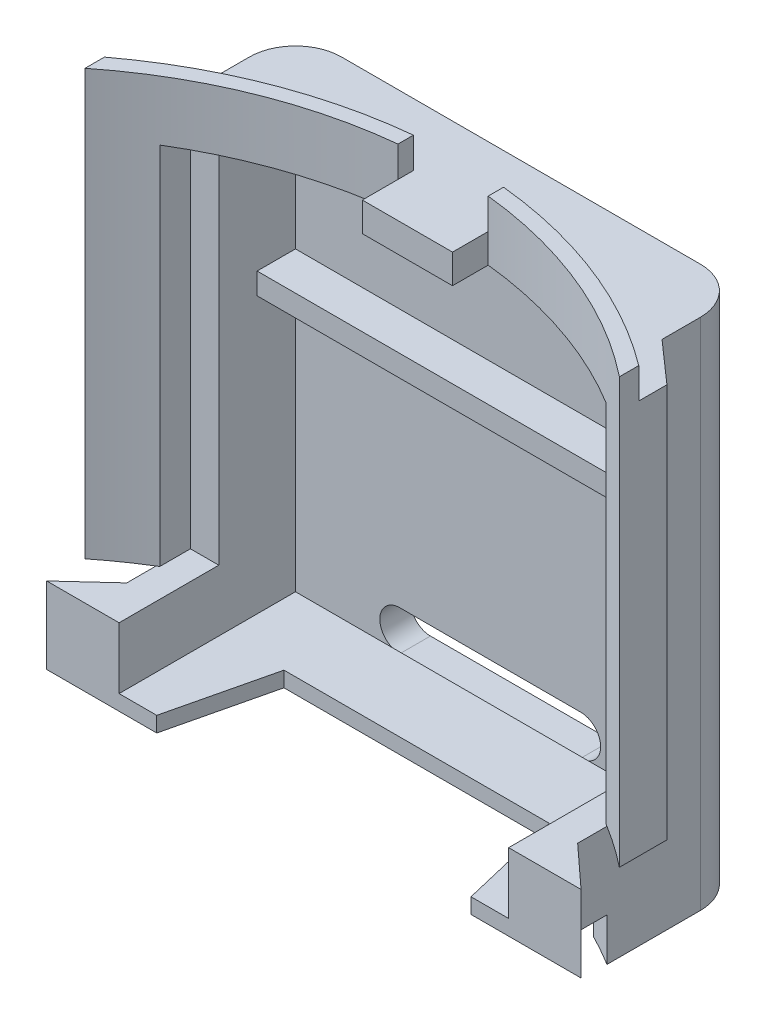
SolidWorks part; units mm, degrees
ref_plane "Спереди" through (0, 0, 0) normal (0, 0, 1) x (1, 0, 0)
ref_plane "Сверху" through (0, 0, 0) normal (0, 1, 0) x (1, 0, 0)
ref_plane "Справа" through (0, 0, 0) normal (1, 0, 0) x (0, 0, -1)
sketch "Эскиз1" plane through (0, 0, 0) normal (0, 1, 0) x (1, 0, 0)
  line L0 (-7.35, 2.75) -> (-7.35, 5.5)
  line L1 (-7.35, 5.5) -> (7.35, 5.5)
  line L2 (7.35, 5.5) -> (7.35, 2.75)
  line L3 (0, 0) -> (0, 5.5) construction
  line L4 (-8.71, 1.55) -> (-8.71, 0)
  line L5 (8.71, 1.55) -> (8.71, 0)
  line L6 (-8.71, 0) -> (8.71, 0) construction
  line L7 (-8.71, 1.55) -> (-7.35, 2.75)
  line L8 (8.71, 1.55) -> (7.35, 2.75)
  arc A0 (-8.71, 0) -> (8.71, 0) centre (0, -10.9607) cw
  dimension "D2" = 14
  dimension "D1" = 14.7
  dimension "D3" = 17.42
  dimension "D4" = 2.75
  dimension "D5" = 5.5
  dimension "D6" = 1.55
extrude "Бобышка-Вытянуть1" add sketch "Эскиз1" along normal blind 17.75
sketch "Эскиз2" plane through (0, 17.75, 0) normal (0, 1, 0) x (1, 0, 0)
  line L0 (8.71, 0) -> (8.71, 1.55) construction
  line L1 (8.71, 1.55) -> (7.35, 2.75) construction
  line L2 (7.35, 2.75) -> (7.35, 5.5) construction
  line L3 (7.35, 5.5) -> (-7.35, 5.5) construction
  line L4 (-7.35, 5.5) -> (-7.35, 2.75) construction
  line L5 (-7.35, 2.75) -> (-8.71, 1.55) construction
  line L6 (-8.71, 1.55) -> (-8.71, 0) construction
  line L7 (8.71, 0.6318) -> (8.71, 1.55)
  line L8 (8.71, 1.55) -> (7.35, 2.75)
  line L9 (7.35, 2.75) -> (7.35, 5.5)
  line L10 (7.35, 5.5) -> (-7.35, 5.5)
  line L11 (-7.35, 5.5) -> (-7.35, 2.75)
  line L12 (-7.35, 2.75) -> (-8.71, 1.55)
  line L13 (-8.71, 1.55) -> (-8.71, 0.6318)
  arc A0 (-8.71, 0.6318) -> (8.71, 0.6318) centre (0, -10.9607) cw
  arc A1 (8.71, 0) -> (-8.71, 0) centre (0, -10.9607) ccw construction
  dimension "D1" = 0.5
extrude "Вырез-Вытянуть1" cut sketch "Эскиз2" against normal blind 1
sketch "Эскиз3" plane through (0, 0, -5.5) normal (0, 0, -1) x (-1, 0, 0)
  line L0 (8.71, 16.75) -> (-8.71, 16.75) construction
  line L1 (-1.47, 17.75) -> (1.47, 17.75)
  line L2 (-1.47, 17.75) -> (-1.47, 16.75)
  line L3 (-1.47, 16.75) -> (1.47, 16.75)
  line L4 (1.47, 17.75) -> (1.47, 16.75)
  line L5 (-1.47, 17.75) -> (1.47, 16.75) construction
  line L6 (-1.47, 16.75) -> (1.47, 17.75) construction
  line L7 (8.71, 17.75) -> (-8.71, 17.75) construction
  point P0 (0, 17.25)
  dimension "D1" = 2.94
extrude "Вырез-Вытянуть2" cut sketch "Эскиз3" against normal through all
sketch "Эскиз4" plane through (0, 0, 0) normal (0, -1, 0) x (1, 0, 0)
  line L0 (-7.35, -2.75) -> (-7.35, -0.9548)
  line L1 (7.35, -2.75) -> (7.35, -0.9548)
  line L2 (-7.35, -2.75) -> (-8.71, -1.55) construction
  line L3 (-8.71, -1.55) -> (-8.71, 0) construction
  line L4 (8.71, -1.55) -> (7.35, -2.75) construction
  line L5 (8.71, 0) -> (8.71, -1.55) construction
  line L6 (-7.35, -2.75) -> (-8.71, -1.55)
  line L7 (-8.71, -1.55) -> (-8.71, 0)
  line L8 (8.71, -1.55) -> (7.35, -2.75)
  line L9 (8.71, 0) -> (8.71, -1.55)
  arc A0 (-8.71, 0) -> (8.71, 0) centre (0, 10.9607) ccw construction
  arc A1 (-8.71, 0) -> (-7.35, -0.9548) centre (0, 10.9607) ccw
  arc A2 (7.35, -0.9548) -> (8.71, 0) centre (0, 10.9607) ccw
extrude "Вырез-Вытянуть3" cut sketch "Эскиз4" against normal blind 3.9
sketch "Эскиз5" plane through (0, 0, 0) normal (0, -1, 0) x (1, 0, 0)
  line L0 (-7.35, -5.5) -> (-7.35, -0.9548) construction
  line L1 (-6.35, -1.5164) -> (6.35, -1.5164)
  line L2 (-6.35, -1.5164) -> (-6.35, -4.5)
  line L3 (-6.35, -4.5) -> (6.35, -4.5)
  line L4 (6.35, -1.5164) -> (6.35, -4.5)
  line L5 (-6.35, -1.5164) -> (6.35, -4.5) construction
  line L6 (-6.35, -4.5) -> (6.35, -1.5164) construction
  line L7 (7.35, -5.5) -> (-7.35, -5.5) construction
  arc A0 (-7.35, -0.9548) -> (7.35, -0.9548) centre (0, 10.9607) ccw construction
  point P0 (0, -3.0082)
  dimension "D1" = 1
  dimension "D2" = 1
extrude "Вырез-Вытянуть4" cut sketch "Эскиз5" against normal blind 1.4
ref_plane "Плоскость1" through (0, 1.9, 0) normal (0, -1, 0) x (-1, 0, 0)
sketch "Эскиз6" plane through (0, 1.9, 0) normal (0, -1, 0) x (-1, 0, 0)
  line L4 (-6.35, 1.5164) -> (6.35, 1.5164)
  line L5 (-6.35, 4.5) -> (-6.35, 1.5164)
  line L6 (6.35, 4.5) -> (-6.35, 4.5)
  line L7 (6.35, 1.5164) -> (6.35, 4.5)
  line L8 (-6.35, 1.5164) -> (6.35, 1.5164)
  line L9 (-6.35, 4.5) -> (-6.35, 1.5164)
  line L10 (6.35, 4.5) -> (-6.35, 4.5)
  line L11 (6.35, 1.5164) -> (6.35, 4.5)
  dimension "D1" = 0
extrude "Вырез-Вытянуть5" cut sketch "Эскиз6" against normal blind 13.9
ref_plane "Плоскость2" through (0, 0, -2) normal (0, 0, -1) x (-1, 0, 0)
sketch "Эскиз7" plane through (0, 0, -2) normal (0, 0, -1) x (-1, 0, 0)
  line L0 (6.35, 15.8) -> (-6.35, 15.8) construction
  line L1 (7.275, 15.8) -> (-7.275, 15.8)
  line L2 (7.275, 15.8) -> (7.275, 3.9)
  line L3 (7.275, 3.9) -> (-7.275, 3.9)
  line L4 (-7.275, 15.8) -> (-7.275, 3.9)
  line L5 (7.275, 15.8) -> (-7.275, 3.9) construction
  line L6 (7.275, 3.9) -> (-7.275, 15.8) construction
  point P0 (0, 9.85)
  dimension "D1" = 14.55
  dimension "D2" = 11.9
extrude "Вырез-Вытянуть6" cut sketch "Эскиз7" against normal through all
sketch "Эскиз8" plane through (0, 1.4, 0) normal (0, -1, 0) x (1, 0, 0)
  line L1 (-7.35, 0) -> (-4.825, 0)
  line L2 (-4.825, 0) -> (-4.325, -2.1)
  line L3 (-4.325, -2.1) -> (4.325, -2.1)
  line L4 (4.325, -2.1) -> (4.825, 0)
  line L5 (4.825, 0) -> (7.35, 0)
  line L7 (7.35, -5.5) -> (-7.35, -5.5) construction
  line L8 (-7.35, -0.9548) -> (-7.35, 0)
  line L9 (7.35, -0.9548) -> (7.35, 0)
  arc A1 (-7.35, -0.9548) -> (7.35, -0.9548) centre (0, 10.9607) ccw
  arc A2 (-6.35, -1.5164) -> (6.35, -1.5164) centre (0, 10.9607) ccw construction
  dimension "D1" = 3.4
  dimension "D2" = 9.65
  dimension "D3" = 8.65
  dimension "D4" = 5.5
extrude "Бобышка-Вытянуть2" add sketch "Эскиз8" against normal up to surface (0.5 mm away) up to face at (0, 1.9, -3.3889)
sketch "Эскиз9" plane through (0, 1.4, 0) normal (0, -1, 0) x (1, 0, 0)
  line L0 (-4.825, 0) -> (-5.1226, 1.25)
  line L1 (-4.325, -2.1) -> (-4.825, 0) construction
  line L2 (4.825, 0) -> (5.1226, 1.25)
  line L3 (4.825, 0) -> (4.325, -2.1) construction
  line L4 (-5.1226, 1.25) -> (-8.71, 1.25)
  line L5 (-8.71, 1.25) -> (-7.35, 0)
  line L6 (-7.35, 0) -> (-4.825, 0)
  line L7 (5.1226, 1.25) -> (8.71, 1.25)
  line L8 (8.71, 1.25) -> (7.35, 0)
  line L9 (7.35, 0) -> (4.825, 0)
  line L10 (7.35, -5.5) -> (-7.35, -5.5) construction
  line L11 (-8.71, 0) -> (-8.71, -1.55) construction
  dimension "D1" = 6.75
extrude "Бобышка-Вытянуть3" add sketch "Эскиз9" against normal up to surface (0.5 mm away) up to face at (0, 1.9, -1.5136)
sketch "Эскиз10" plane through (0, 1.9, 0) normal (0, 1, 0) x (1, 0, 0)
  line L0 (-7.35, 0) -> (-8.71, -1.25) construction
  line L1 (-8.71, -1.25) -> (-5.1226, -1.25) construction
  line L2 (-7.35, 0) -> (-8.71, -1.25)
  line L3 (-8.71, -1.25) -> (-6.35, -1.25)
  line L5 (-6.35, 1.5164) -> (-6.35, -1.25)
  line L6 (-7.35, 0.9548) -> (-7.35, 0) construction
  line L7 (-7.35, 0.9548) -> (-7.35, 0)
  line L8 (7.35, 0) -> (7.35, 0.9548) construction
  line L9 (8.71, -1.25) -> (7.35, 0) construction
  line L10 (5.1226, -1.25) -> (8.71, -1.25) construction
  line L11 (7.35, 0) -> (7.35, 0.9548)
  line L12 (8.71, -1.25) -> (7.35, 0)
  line L13 (6.35, -1.25) -> (8.71, -1.25)
  line L14 (6.35, 1.5164) -> (6.35, -1.25)
  arc A0 (-6.35, 1.5164) -> (-7.35, 0.9548) centre (0, -10.9607) ccw construction
  arc A1 (-6.35, 1.5164) -> (-7.35, 0.9548) centre (0, -10.9607) ccw
  arc A2 (7.35, 0.9548) -> (6.35, 1.5164) centre (0, -10.9607) ccw construction
  arc A3 (7.35, 0.9548) -> (6.35, 1.5164) centre (0, -10.9607) ccw
extrude "Бобышка-Вытянуть4" add sketch "Эскиз10" along normal up to surface (2 mm away) up to face at (8.0335, 3.9, -1.3187)
sketch "Эскиз11" plane through (0, 0, -5.5) normal (0, 0, -1) x (-1, 0, 0)
  line L0 (-2.95, 2.5) -> (2.95, 2.5) construction
  line L1 (-2.95, 3.15) -> (2.95, 3.15)
  line L2 (-2.95, 1.85) -> (2.95, 1.85)
  line L3 (-7.35, 0) -> (7.35, 0) construction
  arc A0 (-2.95, 3.15) -> (-2.95, 1.85) centre (-2.95, 2.5) ccw
  arc A1 (2.95, 1.85) -> (2.95, 3.15) centre (2.95, 2.5) ccw
  point P2 (0, 2.5)
  dimension "D2" = 7.2
  dimension "D1" = 1.3
  dimension "D3" = 1.85
extrude "Вырез-Вытянуть7" cut sketch "Эскиз11" against normal up to surface (1 mm away) up to face at (0, 8.85, -4.5)
sketch "Эскиз12" plane through (0, 0, -4.5) normal (0, 0, 1) x (1, 0, 0)
  line L0 (-6.35, 15.8) -> (-6.35, 1.9) construction
  line L1 (-6.35, 11.58) -> (6.35, 11.58)
  line L2 (-6.35, 11.58) -> (-6.35, 10.88)
  line L3 (-6.35, 10.88) -> (6.35, 10.88)
  line L4 (6.35, 11.58) -> (6.35, 10.88)
  line L5 (6.35, 15.8) -> (6.35, 3.9) construction
  line L6 (-6.35, 15.8) -> (6.35, 15.8) construction
  dimension "D1" = 0.7
  dimension "D2" = 4.22
extrude "Бобышка-Вытянуть5" add sketch "Эскиз12" along normal blind 1.25
fillet "Скругление1" radius 1.5 2 edges at (-7.35, 8.375, -5.5) (7.35, 8.375, -5.5)
sketch "Эскиз13" plane through (0, 16.75, 0) normal (0, 1, 0) x (1, 0, 0)
  line L0 (-1.47, 2.962) -> (-1.47, 1.8)
  line L1 (-1.47, 1.8) -> (1.47, 1.8)
  line L2 (1.47, 1.8) -> (1.47, 2.962)
  line L3 (5.85, 5.5) -> (-5.85, 5.5) construction
  arc A0 (1.47, 2.962) -> (-1.47, 2.962) centre (0, -10.9607) ccw construction
  arc A1 (1.47, 2.962) -> (-1.47, 2.962) centre (0, -10.9607) ccw
  dimension "D1" = 3.7
extrude "Бобышка-Вытянуть6" add sketch "Эскиз13" against normal up to surface (0.95 mm away) up to face at (0, 15.8, -2.63)
